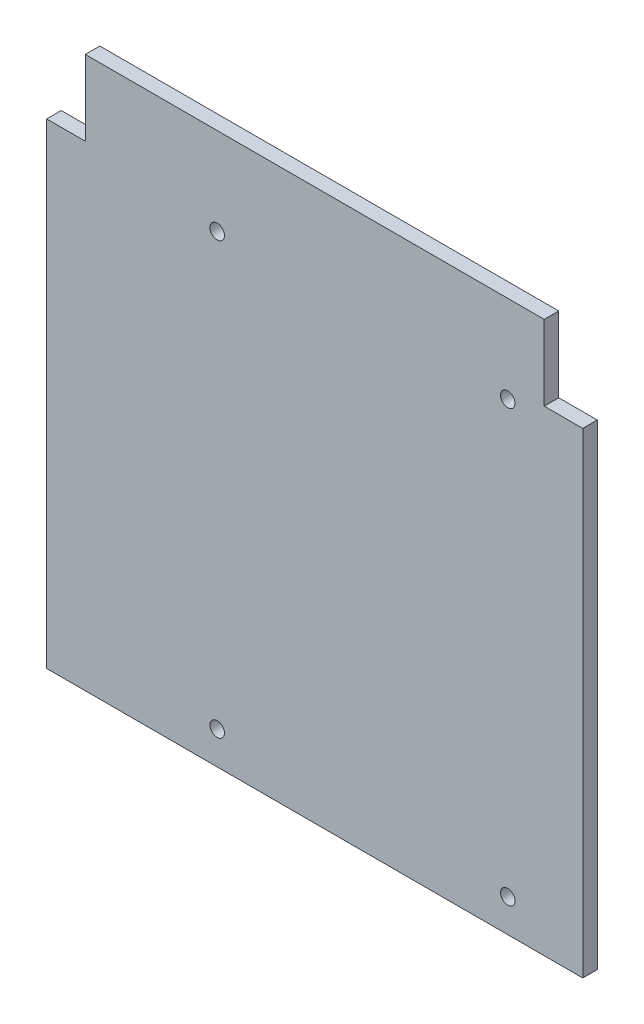
SolidWorks part; units mm, degrees
ref_plane "Front Plane" through (0, 0, 0) normal (0, 0, 1) x (1, 0, 0)
ref_plane "Top Plane" through (0, 0, 0) normal (0, 1, 0) x (1, 0, 0)
ref_plane "Right Plane" through (0, 0, 0) normal (1, 0, 0) x (0, 0, -1)
sketch "Sketch1" plane through (0, 0, 0) normal (0, 0, 1) x (1, 0, 0)
  line L4 (0, -47.5) -> (0, 75.1224) construction
  line L5 (-53.5, -47.5) -> (53.5, -47.5)
  line L6 (-53.5, -47.5) -> (-53.5, 47.5)
  line L7 (-53.5, 47.5) -> (-45.802, 47.5)
  line L8 (53.5, -47.5) -> (53.5, 47.5)
  line L9 (-53.5, -47.5) -> (53.5, 47.5) construction
  line L10 (-53.5, 47.5) -> (53.5, -47.5) construction
  line L11 (0, 0) -> (92.3064, 0) construction
  line L12 (48, 57.5289) -> (48, -67.5733) construction
  line L13 (-48, 56.5105) -> (-48, -72.884) construction
  line L14 (-43, -16.4523) -> (42, -16.4523) construction
  line L15 (38.5367, -54.9766) -> (38.5367, 45.0477) construction
  line L16 (42.0367, 11.5477) -> (-43.0367, 11.5477) construction
  line L17 (42.0367, 11.5477) -> (42.0367, -44.4523) construction
  line L18 (42.0367, -44.4523) -> (-43.0367, -44.4523) construction
  line L19 (-43.0367, 11.5477) -> (-43.0367, -44.4523) construction
  line L20 (42.0367, 11.5477) -> (-43.0367, -44.4523) construction
  line L21 (42.0367, -44.4523) -> (-43.0367, 11.5477) construction
  line L22 (38.5367, -40.9523) -> (-19.4633, -40.9523) construction
  line L23 (38.5367, 45.0477) -> (-19.4633, 45.0477) construction
  line L24 (45.802, 47.5) -> (53.5, 47.5)
  line L26 (45.802, 47.5) -> (45.802, 62.5)
  line L27 (45.802, 62.5) -> (-45.802, 62.5)
  line L28 (-45.802, 47.5) -> (-45.802, 62.5)
  line L29 (45.802, 16.5583) -> (-45.802, 62.5) construction
  line L30 (45.802, 62.5) -> (-45.802, 16.5583) construction
  circle A0 centre (38.5367, -40.9523) radius 1.45
  circle A1 centre (38.5367, 45.0477) radius 1.45
  circle A2 centre (-19.4633, -40.9523) radius 1.45
  circle A3 centre (-19.4633, 45.0477) radius 1.45
  point P0 (0, 0)
  point P12 (-0.5, -16.4523)
  point P15 (-0.5, -16.4523)
  point P31 (0, -47.5)
  point P32 (0, 39.5291)
  dimension "D3" = 5.5
  dimension "D10" = 2.9
  dimension "D11" = 2.9
  dimension "D13" = 2.9
  dimension "D14" = 2.9
  dimension "D1" = 107
  dimension "D2" = 95
  dimension "D4" = 5.5
  dimension "D5" = 85
  dimension "D6" = 56
  dimension "D7" = 3.5
  dimension "D8" = 3.5
  dimension "D9" = 86
  dimension "D12" = 58
  dimension "D15" = 58
  dimension "D16" = 0.5
  dimension "D17" = 15
extrude "Boss-Extrude2" add sketch "Sketch1" along normal blind 2.9
